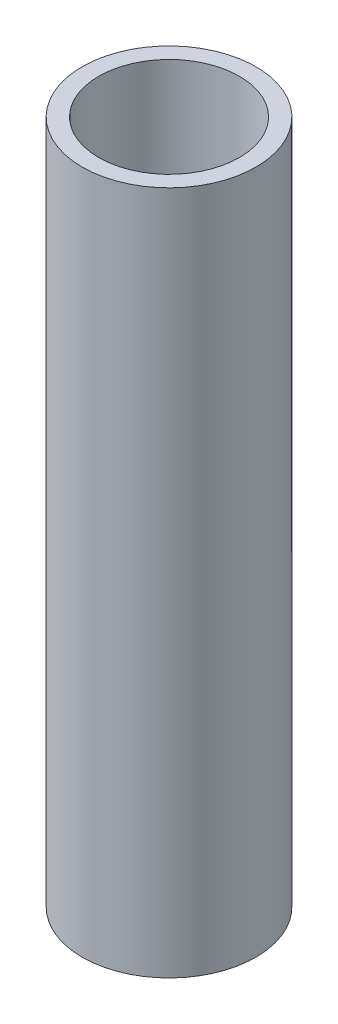
SolidWorks part; units mm, degrees
ref_plane "Front Plane" through (0, 0, 0) normal (0, 0, 1) x (1, 0, 0)
ref_plane "Top Plane" through (0, 0, 0) normal (0, 1, 0) x (1, 0, 0)
ref_plane "Right Plane" through (0, 0, 0) normal (1, 0, 0) x (0, 0, -1)
sketch "Sketch1" plane through (0, 0, 0) normal (0, 1, 0) x (1, 0, 0)
  circle A0 centre (0, 0) radius 12.7
  circle A1 centre (0, 0) radius 10.287
  dimension "D1" = 25.4
  dimension "D2" = 2.413
extrude "Boss-Extrude1" add sketch "Sketch1" along normal blind 100
